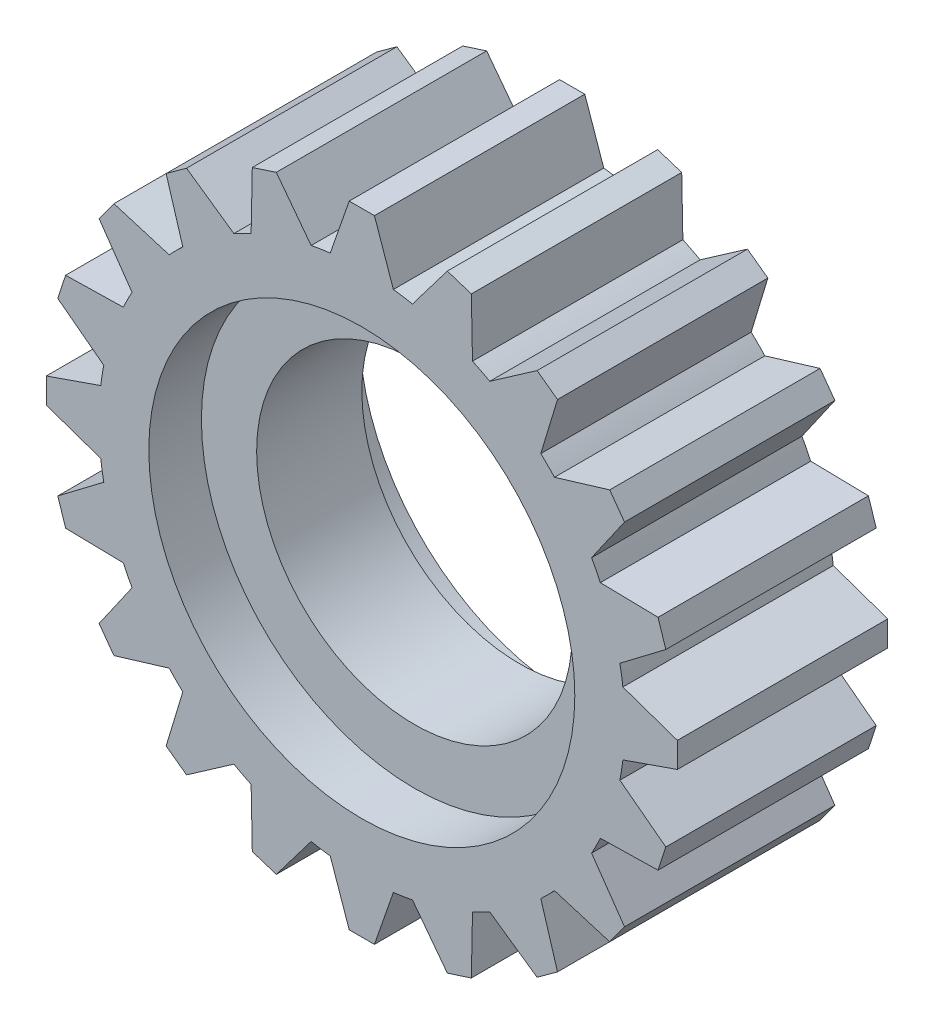
SolidWorks part; units mm, degrees
ref_plane "Front Plane" through (0, 0, 0) normal (0, 0, 1) x (1, 0, 0)
ref_plane "Top Plane" through (0, 0, 0) normal (0, 1, 0) x (1, 0, 0)
ref_plane "Right Plane" through (0, 0, 0) normal (1, 0, 0) x (0, 0, -1)
sketch "Sketch1" plane through (0, 0, 0) normal (0, 0, 1) x (1, 0, 0)
  line L0 (0, 34.3548) -> (0, -34.3548) construction
  line L1 (-35.8199, 0) -> (35.8199, 0) construction
  line L2 (-1.2, 30) -> (1.2, 30)
  line L3 (-1.2, 30) -> (-3, 24.8193)
  line L4 (1.2, 30) -> (3, 24.8193)
  line L5 (8.1292, 28.9025) -> (4.8164, 24.5317)
  line L6 (8.1292, 28.9025) -> (10.4118, 28.1609)
  line L7 (10.4118, 28.1609) -> (10.5228, 22.6776)
  line L8 (16.6627, 24.9759) -> (12.1614, 21.8426)
  line L9 (16.6627, 24.9759) -> (18.6044, 23.5652)
  line L10 (18.6044, 23.5652) -> (17.0155, 18.3159)
  line L11 (23.5652, 18.6044) -> (18.3159, 17.0155)
  line L12 (23.5652, 18.6044) -> (24.9759, 16.6627)
  line L13 (24.9759, 16.6627) -> (21.8426, 12.1614)
  line L14 (28.1609, 10.4118) -> (22.6776, 10.5228)
  line L15 (28.1609, 10.4118) -> (28.9025, 8.1292)
  line L16 (28.9025, 8.1292) -> (24.5317, 4.8164)
  line L17 (30, 1.2) -> (24.8193, 3)
  line L18 (30, 1.2) -> (30, -1.2)
  line L19 (30, -1.2) -> (24.8193, -3)
  line L20 (28.9025, -8.1292) -> (24.5317, -4.8164)
  line L21 (28.9025, -8.1292) -> (28.1609, -10.4118)
  line L22 (28.1609, -10.4118) -> (22.6776, -10.5228)
  line L23 (24.9759, -16.6627) -> (21.8426, -12.1614)
  line L24 (24.9759, -16.6627) -> (23.5652, -18.6044)
  line L25 (23.5652, -18.6044) -> (18.3159, -17.0155)
  line L26 (18.6044, -23.5652) -> (17.0155, -18.3159)
  line L27 (18.6044, -23.5652) -> (16.6627, -24.9759)
  line L28 (16.6627, -24.9759) -> (12.1614, -21.8426)
  line L29 (10.4118, -28.1609) -> (10.5228, -22.6776)
  line L30 (10.4118, -28.1609) -> (8.1292, -28.9025)
  line L31 (8.1292, -28.9025) -> (4.8164, -24.5317)
  line L32 (1.2, -30) -> (3, -24.8193)
  line L33 (1.2, -30) -> (-1.2, -30)
  line L34 (-1.2, -30) -> (-3, -24.8193)
  line L35 (-8.1292, -28.9025) -> (-4.8164, -24.5317)
  line L36 (-8.1292, -28.9025) -> (-10.4118, -28.1609)
  line L37 (-10.4118, -28.1609) -> (-10.5228, -22.6776)
  line L38 (-16.6627, -24.9759) -> (-12.1614, -21.8426)
  line L39 (-16.6627, -24.9759) -> (-18.6044, -23.5652)
  line L40 (-18.6044, -23.5652) -> (-17.0155, -18.3159)
  line L41 (-23.5652, -18.6044) -> (-18.3159, -17.0155)
  line L42 (-23.5652, -18.6044) -> (-24.9759, -16.6627)
  line L43 (-24.9759, -16.6627) -> (-21.8426, -12.1614)
  line L44 (-28.1609, -10.4118) -> (-22.6776, -10.5228)
  line L45 (-28.1609, -10.4118) -> (-28.9025, -8.1292)
  line L46 (-28.9025, -8.1292) -> (-24.5317, -4.8164)
  line L47 (-30, -1.2) -> (-24.8193, -3)
  line L48 (-30, -1.2) -> (-30, 1.2)
  line L49 (-30, 1.2) -> (-24.8193, 3)
  line L50 (-28.9025, 8.1292) -> (-24.5317, 4.8164)
  line L51 (-28.9025, 8.1292) -> (-28.1609, 10.4118)
  line L52 (-28.1609, 10.4118) -> (-22.6776, 10.5228)
  line L53 (-24.9759, 16.6627) -> (-21.8426, 12.1614)
  line L54 (-24.9759, 16.6627) -> (-23.5652, 18.6044)
  line L55 (-23.5652, 18.6044) -> (-18.3159, 17.0155)
  line L56 (-18.6044, 23.5652) -> (-17.0155, 18.3159)
  line L57 (-18.6044, 23.5652) -> (-16.6627, 24.9759)
  line L58 (-16.6627, 24.9759) -> (-12.1614, 21.8426)
  line L59 (-10.4118, 28.1609) -> (-10.5228, 22.6776)
  line L60 (-10.4118, 28.1609) -> (-8.1292, 28.9025)
  line L61 (-8.1292, 28.9025) -> (-4.8164, 24.5317)
  arc A2 (-3, 24.8193) -> (-4.8164, 24.5317) centre (0, 0) ccw
  arc A3 (4.8164, 24.5317) -> (3, 24.8193) centre (0, 0) ccw
  arc A4 (12.1614, 21.8426) -> (10.5228, 22.6776) centre (0, 0) ccw
  arc A5 (18.3159, 17.0155) -> (17.0155, 18.3159) centre (0, 0) ccw
  arc A6 (22.6776, 10.5228) -> (21.8426, 12.1614) centre (0, 0) ccw
  arc A7 (24.8193, 3) -> (24.5317, 4.8164) centre (0, 0) ccw
  arc A8 (24.5317, -4.8164) -> (24.8193, -3) centre (0, 0) ccw
  arc A9 (21.8426, -12.1614) -> (22.6776, -10.5228) centre (0, 0) ccw
  arc A10 (17.0155, -18.3159) -> (18.3159, -17.0155) centre (0, 0) ccw
  arc A11 (10.5228, -22.6776) -> (12.1614, -21.8426) centre (0, 0) ccw
  arc A12 (3, -24.8193) -> (4.8164, -24.5317) centre (0, 0) ccw
  arc A13 (-4.8164, -24.5317) -> (-3, -24.8193) centre (0, 0) ccw
  arc A14 (-12.1614, -21.8426) -> (-10.5228, -22.6776) centre (0, 0) ccw
  arc A15 (-18.3159, -17.0155) -> (-17.0155, -18.3159) centre (0, 0) ccw
  arc A16 (-22.6776, -10.5228) -> (-21.8426, -12.1614) centre (0, 0) ccw
  arc A17 (-24.8193, -3) -> (-24.5317, -4.8164) centre (0, 0) ccw
  arc A18 (-24.5317, 4.8164) -> (-24.8193, 3) centre (0, 0) ccw
  arc A19 (-21.8426, 12.1614) -> (-22.6776, 10.5228) centre (0, 0) ccw
  arc A20 (-17.0155, 18.3159) -> (-18.3159, 17.0155) centre (0, 0) ccw
  arc A21 (-10.5228, 22.6776) -> (-12.1614, 21.8426) centre (0, 0) ccw
  circle A22 centre (0, 0) radius 20.25
  circle A23 centre (0, 0) radius 15
  point P6 (0, 0)
  point P9 (0, 0)
  point P12 (0, 31.0037)
  point P14 (0, 30)
  point P93 (0, 0)
  dimension "D1" = 50
  dimension "D6" = 40.5
  dimension "D7" = 30
  dimension "D2" = 1.2
  dimension "D3" = 3
  dimension "D4" = 30
  dimension "D5" = 20
extrude "Boss-Extrude1" add sketch "Sketch1" along normal blind 10 and the other way blind 10 contours A17 L46 L45 L44 A16 L43 L42 L41 A15 L40 L39 L38 A14 L37 L36 L35 A13 L34 L33 L32 A12 L31 L30 L29 A11 L28 L27 L26 A10 L25 L24 L23 A9 L22 L21 L20 A8 L19 L18 L17 A7 L16 L15 L14 A6 L13 L12 L11 A5 L10 L9 L8 A4 L7 L6 L5 A3 L4 L2 L3 A2 L61 L60 L59 A21 L58 L57 L56 A20 L55 L54 L53 A19 L52 L51 L50 A18 L49 L48 L47 | A23
sketch "Sketch2" plane through (0, 0, 10) normal (0, 0, 1) x (1, 0, 0)
  circle A0 centre (0, 0) radius 20.25
  dimension "D1" = 40.5
extrude "Cut-Extrude1" cut sketch "Sketch2" against normal blind 5
mirror "Mirror1" about plane through (0, 0, 0) normal (0, 0, 1) of "Cut-Extrude1"
